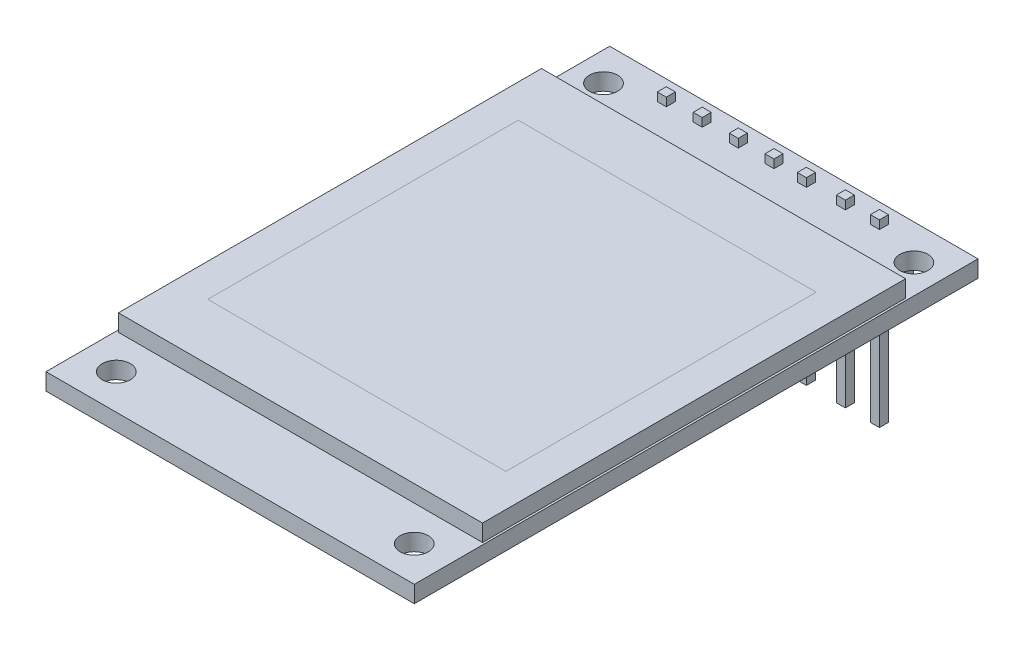
SolidWorks part; units mm, degrees
ref_plane "前视基准面" through (0, 0, 0) normal (0, 0, 1) x (1, 0, 0)
ref_plane "上视基准面" through (0, 0, 0) normal (0, 1, 0) x (1, 0, 0)
ref_plane "右视基准面" through (0, 0, 0) normal (1, 0, 0) x (0, 0, -1)
sketch "PCB底板草图" plane through (0, 0, 0) normal (0, 1, 0) x (1, 0, 0)
  line L0 (-13.1, -20.05) -> (13.1, -20.05)
  line L2 (-13.1, -20.05) -> (-13.1, 20.05)
  line L3 (-13.1, 20.05) -> (13.1, 20.05)
  line L4 (13.1, -20.05) -> (13.1, 20.05)
  line L8 (-12.95, 15.05) -> (12.95, 15.05)
  line L9 (-12.95, 15.05) -> (-12.95, -15.05)
  line L10 (-12.95, -15.05) -> (12.95, -15.05)
  line L11 (12.95, -15.05) -> (12.95, 15.05)
  circle A0 centre (-10.6, -17.55) radius 1
  circle A1 centre (10.6, -17.55) radius 1
  circle A4 centre (11.04, 17.55) radius 1
  circle A5 centre (-11.04, 17.55) radius 1
  point P0 (0, 0)
extrude "PCB底板" add sketch "PCB底板草图" along normal blind 1.2 contours L10 L11 L8 L9 | L0 L4 L3 L2 A5 A4 A1 A0 L11 L10 L9 L8 region at (-13.0521, 0, 0) region at (0, 0, 0)
sketch "OLED面板草图" plane through (0, 1.2, 0) normal (0, 1, 0) x (1, 0, 0)
  line L1 (-12.95, -15.05) -> (12.95, -15.05)
  line L2 (-12.95, -15.05) -> (-12.95, 15.05)
  line L3 (-12.95, 15.05) -> (12.95, 15.05)
  line L4 (12.95, -15.05) -> (12.95, 15.05)
  line L5 (-10.6, -11.04) -> (10.6, -11.04)
  line L6 (-10.6, -11.04) -> (-10.6, 11.04)
  line L7 (-10.6, 11.04) -> (10.6, 11.04)
  line L8 (10.6, -11.04) -> (10.6, 11.04)
  point P0 (0, 0)
  point P6 (0, 0)
extrude "OLED面板黑框" add sketch "OLED面板草图" along normal blind 1.2 separate body
extrude "OLED面板" add sketch "OLED面板草图<2>" along normal blind 1.2 separate body contours L5 L8 L7 L6 region at (0, 1.2, 0)
sketch "OLED面板草图<2>" plane through (0, 1.2, 0) normal (0, 1, 0) x (1, 0, 0) same geometry as "OLED面板草图"
sketch "2.54端子草图" plane through (0, 0, 0) normal (0, -1, 0) x (1, 0, 0)
  line L2 (7.79, -18.3477) -> (7.15, -18.3477)
  line L4 (7.79, -18.3477) -> (7.79, -18.9877)
  line L5 (8.74, -17.28) -> (6.2, -17.28)
  line L6 (8.74, -17.28) -> (8.74, -19.82)
  line L7 (8.74, -19.82) -> (6.2, -19.82)
  line L8 (6.2, -17.28) -> (6.2, -19.82)
  line L11 (6.2, -19.82) -> (3.66, -19.82)
  line L12 (6.2, -19.82) -> (6.2, -17.28)
  line L13 (6.2, -17.28) -> (3.66, -17.28)
  line L14 (3.66, -19.82) -> (3.66, -17.28)
  line L15 (3.66, -19.82) -> (1.12, -19.82)
  line L16 (3.66, -19.82) -> (3.66, -17.28)
  line L17 (3.66, -17.28) -> (1.12, -17.28)
  line L18 (1.12, -19.82) -> (1.12, -17.28)
  line L19 (1.12, -19.82) -> (-1.42, -19.82)
  line L20 (1.12, -19.82) -> (1.12, -17.28)
  line L21 (1.12, -17.28) -> (-1.42, -17.28)
  line L22 (-1.42, -19.82) -> (-1.42, -17.28)
  line L23 (-1.42, -19.82) -> (-3.96, -19.82)
  line L24 (-1.42, -19.82) -> (-1.42, -17.28)
  line L25 (-1.42, -17.28) -> (-3.96, -17.28)
  line L26 (-3.96, -19.82) -> (-3.96, -17.28)
  line L27 (-3.96, -19.82) -> (-6.5, -19.82)
  line L28 (-3.96, -19.82) -> (-3.96, -17.28)
  line L29 (-3.96, -17.28) -> (-6.5, -17.28)
  line L30 (-6.5, -19.82) -> (-6.5, -17.28)
  line L31 (-6.5, -19.82) -> (-9.04, -19.82)
  line L32 (-6.5, -19.82) -> (-6.5, -17.28)
  line L33 (-6.5, -17.28) -> (-9.04, -17.28)
  line L34 (-9.04, -19.82) -> (-9.04, -17.28)
  line L35 (7.79, -18.9877) -> (7.15, -18.9877)
  line L36 (7.15, -18.3477) -> (7.15, -18.9877)
  line L42 (5.3677, -18.3477) -> (4.7277, -18.3477)
  line L43 (5.3677, -18.3477) -> (5.3677, -18.9877)
  line L44 (5.3677, -18.9877) -> (4.7277, -18.9877)
  line L45 (4.7277, -18.3477) -> (4.7277, -18.9877)
  line L47 (5.3677, -18.9877) -> (4.7277, -18.3477) construction
  line L48 (2.5923, -18.3477) -> (1.9523, -18.3477)
  line L49 (2.5923, -18.3477) -> (2.5923, -18.9877)
  line L50 (2.5923, -18.9877) -> (1.9523, -18.9877)
  line L51 (1.9523, -18.3477) -> (1.9523, -18.9877)
  line L54 (0.2877, -18.3477) -> (-0.3523, -18.3477)
  line L55 (0.2877, -18.3477) -> (0.2877, -18.9877)
  line L56 (0.2877, -18.9877) -> (-0.3523, -18.9877)
  line L57 (-0.3523, -18.3477) -> (-0.3523, -18.9877)
  line L60 (-2.2523, -18.3477) -> (-2.8923, -18.3477)
  line L61 (-2.2523, -18.3477) -> (-2.2523, -18.9877)
  line L62 (-2.2523, -18.9877) -> (-2.8923, -18.9877)
  line L63 (-2.8923, -18.3477) -> (-2.8923, -18.9877)
  line L66 (-4.8164, -18.3477) -> (-5.4564, -18.3477)
  line L67 (-4.8164, -18.3477) -> (-4.8164, -18.9877)
  line L68 (-4.8164, -18.9877) -> (-5.4564, -18.9877)
  line L69 (-5.4564, -18.3477) -> (-5.4564, -18.9877)
  line L72 (-7.3523, -18.3277) -> (-7.9923, -18.3277)
  line L73 (-7.3523, -18.3277) -> (-7.3523, -18.9677)
  line L74 (-7.3523, -18.9677) -> (-7.9923, -18.9677)
  line L75 (-7.9923, -18.3277) -> (-7.9923, -18.9677)
  point P0 (7.47, -18.6677)
  point P4 (0, 0)
  point P6 (0, 0)
  point P7 (0, 0)
  point P8 (5.0477, -18.6677)
  point P29 (2.2723, -18.6677)
  point P34 (-0.0323, -18.6677)
  point P39 (-2.5723, -18.6677)
  point P44 (-5.1364, -18.6677)
  point P49 (-7.6723, -18.6477)
  point P54 (0, 0)
  point P55 (0, 0)
  point P56 (0, 0)
extrude "2.54端子0" add sketch "2.54端子草图" along normal blind 2.5 contours L5 L8 L7 L6 L36 L2 L4 L35 | L14 L11 L8 L13 L45 L42 L43 L44 | L18 L15 L14 L17 L51 L48 L49 L50 | L22 L19 L18 L21 L57 L54 L55 L56 | L26 L23 L22 L25 L63 L60 L61 L62 | L30 L27 L26 L29 L69 L66 L67 L68 | L34 L31 L30 L33 L75 L72 L73 L74 region at (8.7041, 0, -18.55) region at (6.1641, 0, -18.55) region at (3.6241, 0, -18.55) region at (1.0841, 0, -18.55) region at (-1.4559, 0, -18.55) region at (-3.9959, 0, -18.55) region at (-6.5359, 0, -18.55)
extrude "2.54端子1" add sketch "2.54端子草图<3>" along normal blind 11 and the other way blind 1.8 contours L2 L36 L35 L4 | L44 L47 L45 | L48 L51 L50 L49 | L54 L57 L56 L55 | L60 L63 L62 L61 | L66 L69 L68 L67 | L72 L75 L74 L73 | L43 L42 L45 L44 region at (7.47, 0, -18.6677) region at (4.941, 0, -18.7743) region at (2.2723, 0, -18.6677) region at (-0.0323, 0, -18.6677) region at (-2.5723, 0, -18.6677) region at (-5.1364, 0, -18.6677) region at (-7.6723, 0, -18.6477)
sketch "2.54端子草图<3>" plane through (0, 0, 0) normal (0, -1, 0) x (1, 0, 0) same geometry as "2.54端子草图"
